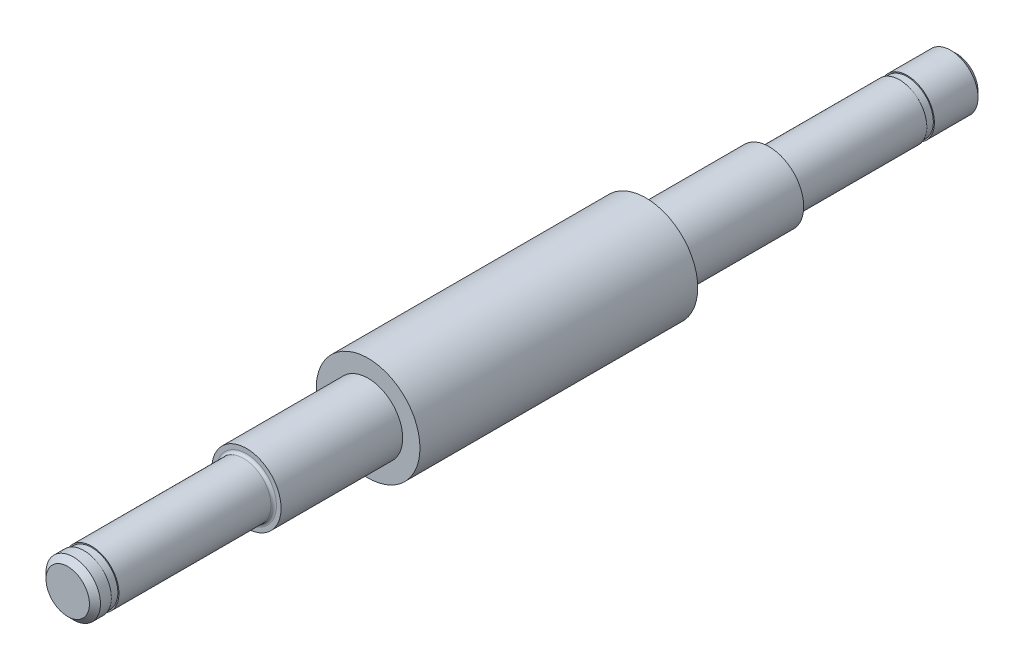
SolidWorks part; units mm, degrees
ref_plane "Front Plane" through (0, 0, 0) normal (0, 0, 1) x (1, 0, 0)
ref_plane "Top Plane" through (0, 0, 0) normal (0, 1, 0) x (1, 0, 0)
ref_plane "Right Plane" through (0, 0, 0) normal (1, 0, 0) x (0, 0, -1)
sketch "Sketch1" plane through (0, 0, 0) normal (0, 0, 1) x (1, 0, 0)
  circle A0 centre (0, 0) radius 2.5
  dimension "D1" = 5
extrude "Boss-Extrude1" add sketch "Sketch1" along normal mid plane 81.534
ref_axis "Axis1" through (0, 0, 40.767) along (0, 0, -1)
sketch "Sketch2" plane through (0, 0, 0) normal (1, 0, 0) x (0, 0, -1)
  line L0 (40.767, 2.5) -> (-40.767, 2.5) construction
  line L1 (-39.2646, 2.5) -> (-38.5646, 2.5)
  line L2 (-39.2646, 2.5) -> (-39.2646, 2.4)
  line L3 (-39.2646, 2.4) -> (-38.5646, 2.4)
  line L4 (-38.5646, 2.5) -> (-38.5646, 2.4)
  line L5 (-38.5646, -75.1766) -> (-38.5646, -68.8261) construction
  dimension "D1" = 0.1
  dimension "D2" = 0.7
revolve "Cut-Revolve1" cut sketch "Sketch2" angle 360 about axis through (0, 0, 40.767) along (0, 0, -1)
sketch "Sketch4" plane through (0, 0, -40.767) normal (0, 0, -1) x (-1, 0, 0)
  circle A0 centre (0, 0) radius 3.4022
extrude "Boss-Extrude2" [suppressed] add sketch "Sketch4" against normal up to surface (5.1753 mm away)
sketch "Sketch5" plane through (0, 0, 24.3646) normal (0, 0, -1) x (-1, 0, 0)
  circle A0 centre (0, 0) radius 3.175
  dimension "D1" = 6.35
extrude "Boss-Extrude3" add sketch "Sketch5" along normal blind 47.9552
ref_axis "Axis2" through (0, 0, -23.5906) along (0, 0, -1)
sketch "Sketch7" plane through (0, -92.7159, 0) normal (1, 0, 0) x (0, 0, 1)
  line L0 (-40.767, -95.2159) -> (-23.5906, -95.2159) construction
  line L1 (-36.262, -95.1159) -> (-35.562, -95.1159)
  line L2 (-36.262, -95.1159) -> (-36.262, -95.2159)
  line L3 (-36.262, -95.2159) -> (-35.562, -95.2159)
  line L4 (-35.562, -95.1159) -> (-35.562, -95.2159)
  dimension "D1" = 0.7
  dimension "D2" = 0.1
revolve "Cut-Revolve2" cut sketch "Sketch7" angle 360 about axis through (0, 0, -23.5906) along (0, 0, -1)
chamfer "Chamfer1" distance 0.508 angle 45 2 edges at (2.5, 0, 40.767) (2.5, 0, -40.767)
fillet "Fillet1" radius 0.254 2 edges at (-2.5, 0, -23.5906) (-2.5, 0, 24.3646)
sketch "Sketch8" plane through (0, 0, 0) normal (0, 0, 1) x (1, 0, 0)
  circle A0 centre (0, 0) radius 4.7625
  dimension "D1" = 9.525
extrude "Boss-Extrude4" add sketch "Sketch8" along normal blind 13.208 and the other way blind 12.2809
